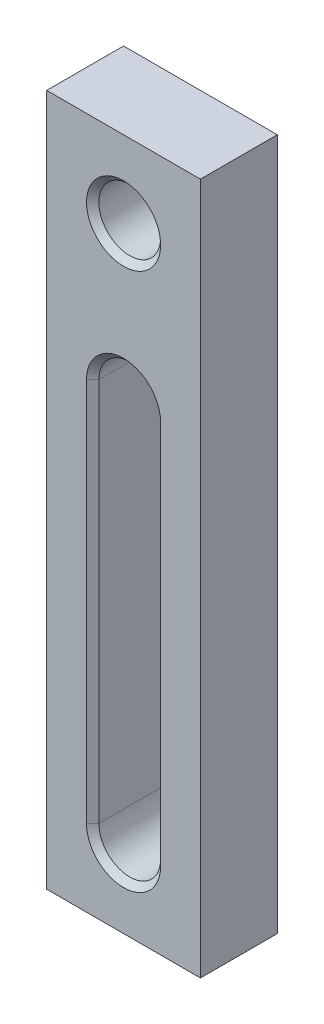
SolidWorks part; units mm, degrees
material "Простая углеродистая сталь"
ref_plane "Спереди" through (0, 0, 0) normal (0, 0, 1) x (1, 0, 0)
ref_plane "Сверху" through (0, 0, 0) normal (0, 1, 0) x (1, 0, 0)
ref_plane "Справа" through (0, 0, 0) normal (1, 0, 0) x (0, 0, -1)
sketch "Эскиз1" plane through (0, 0, 0) normal (0, 0, 1) x (1, 0, 0)
  line L1 (0, 0) -> (50, 0)
  line L2 (0, 0) -> (0, 225)
  line L3 (0, 225) -> (50, 225)
  line L4 (50, 0) -> (50, 225)
  dimension "D1" = 50
  dimension "D2" = 225
extrude "Бобышка-Вытянуть1" add sketch "Эскиз1" along normal blind 25
sketch "Эскиз2" plane through (0, 0, 25) normal (0, 0, 1) x (1, 0, 0)
  line L1 (14.95, 25) -> (14.95, 150)
  line L2 (35.05, 25) -> (35.05, 150)
  line L3 (0, 225) -> (0, 0) construction
  line L4 (0, 0) -> (50, 0) construction
  arc A0 (14.95, 25) -> (35.05, 25) centre (25, 25) ccw
  arc A1 (14.95, 150) -> (35.05, 150) centre (25, 150) cw
  circle A2 centre (25, 200) radius 10.05
  point P7 (14.95, 87.5)
  point P10 (35.05, 87.5)
  dimension "D1" = 25
  dimension "D2" = 25
extrude "Вырез-Вытянуть1" cut sketch "Эскиз2" against normal through all
chamfer "Фаска1" distance 2 angle 45 10 edges at (14.95, 87.5, 0) (25, 14.95, 0) (25, 160.05, 0) (35.05, 87.5, 0) (35.05, 87.5, 25) (25, 160.05, 25) (25, 14.95, 25) (14.95, 87.5, 25) (35.05, 200, 0) (35.05, 200, 25)
